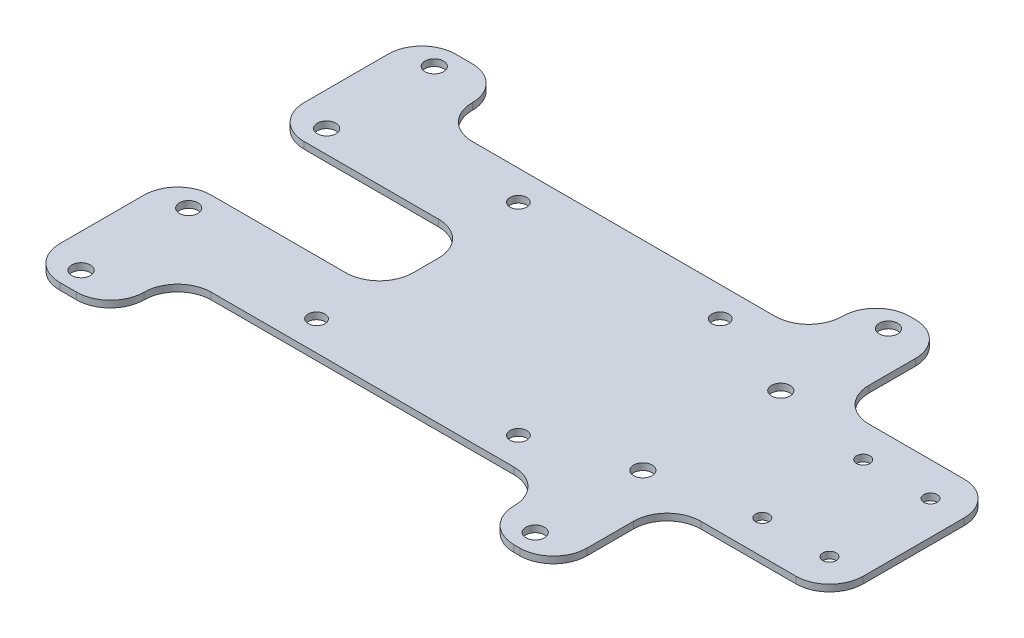
SolidWorks part; units mm, degrees
ref_plane "Front Plane" through (0, 0, 0) normal (0, 0, 1) x (1, 0, 0)
ref_plane "Top Plane" through (0, 0, 0) normal (0, 1, 0) x (1, 0, 0)
ref_plane "Right Plane" through (0, 0, 0) normal (1, 0, 0) x (0, 0, -1)
sketch "Sketch1" plane through (0, 0, 0) normal (0, 1, 0) x (1, 0, 0)
  line L2 (0, 0) -> (0, 140)
  line L12 (80, 0) -> (80, 140)
  line L14 (80, 0) -> (0, 0)
  line L15 (80, 140) -> (0, 140)
  point P0 (0, 0)
  dimension "D1" = 80
  dimension "D2" = 140
extrude "Boss-Extrude1" add sketch "Sketch1" along normal blind 2 contours L2 region at (40, 0, -70)
sketch "Sketch4" plane through (80, 0, 0) normal (1, 0, 0) x (0, 0, -1)
  line L1 (0, 0) -> (140, 0)
  line L2 (0, 0) -> (0, 2)
  line L3 (0, 2) -> (140, 2)
  line L4 (140, 0) -> (140, 2)
extrude "Boss-Extrude2" add sketch "Sketch4" along normal blind 35
sketch "Sketch5" plane through (115, 0, 0) normal (1, 0, 0) x (0, 0, -1)
  line L4 (0, 2) -> (0, 0)
  line L5 (0, 0) -> (140, 0)
  line L6 (140, 0) -> (140, 2)
  line L7 (140, 2) -> (0, 2)
  line L8 (0, 2) -> (0, 0)
  line L9 (0, 0) -> (140, 0)
  line L10 (140, 0) -> (140, 2)
  line L11 (140, 2) -> (0, 2)
  dimension "D1" = 0
extrude "Boss-Extrude3" add sketch "Sketch5" along normal blind 20
sketch "Sketch2" plane through (0, 0, 0) normal (0, -1, 0) x (1, 0, 0)
  line L0 (67.5, 0) -> (67.5, -140) construction
  line L1 (135, 0) -> (0, 0) construction
  line L2 (135, -140) -> (0, -140) construction
  line L4 (57.5, 0) -> (77.5, 0) construction
  line L5 (57.5, 0) -> (57.5, -140) construction
  line L6 (57.5, -140) -> (77.5, -140) construction
  line L7 (77.5, 0) -> (77.5, -140) construction
  line L8 (57.5, 0) -> (77.5, -140) construction
  line L9 (57.5, -140) -> (77.5, 0) construction
  line L10 (37.5, 0) -> (97.5, 0) construction
  line L11 (37.5, 0) -> (37.5, -140) construction
  line L12 (37.5, -140) -> (97.5, -140) construction
  line L13 (97.5, 0) -> (97.5, -140) construction
  line L14 (37.5, 0) -> (97.5, -140) construction
  line L15 (37.5, -140) -> (97.5, 0) construction
  circle A0 centre (97.5, -100) radius 2.5
  circle A1 centre (97.5, -40) radius 2.5
  circle A2 centre (37.5, -40) radius 2.5
  circle A3 centre (37.5, -100) radius 2.5
  point P6 (67.5, -70)
  point P11 (67.5, -70)
  dimension "D7" = 5
  dimension "D8" = 5
  dimension "D9" = 5
  dimension "D10" = 5
  dimension "D1" = 20
  dimension "D2" = 60
  dimension "D4" = 60
  dimension "D6" = 60
extrude "Cut-Extrude1" cut sketch "Sketch2" against normal blind 10
sketch "Sketch7" plane through (0, 0, 0) normal (-1, 0, 0) x (0, 0, 1)
  line L4 (-140, 0) -> (0, 0)
  line L5 (0, 0) -> (0, 2)
  line L6 (0, 2) -> (-140, 2)
  line L7 (-140, 2) -> (-140, 0)
  line L8 (-140, 0) -> (0, 0)
  line L9 (0, 0) -> (0, 2)
  line L10 (0, 2) -> (-140, 2)
  line L11 (-140, 2) -> (-140, 0)
  dimension "D1" = 0
extrude "Boss-Extrude5" add sketch "Sketch7" along normal blind 20
sketch "Sketch8" plane through (0, 0, 0) normal (0, -1, 0) x (1, 0, 0)
  line L0 (125, 0) -> (125, -140) construction
  line L1 (135, 0) -> (-20, 0) construction
  line L2 (135, -140) -> (-20, -140) construction
  line L3 (135, 0) -> (135, -140) construction
  line L4 (135, -140) -> (-20, -140) construction
  line L5 (57.5, -140) -> (57.5, 0) construction
  circle A0 centre (125, -17.5) radius 2.75
  circle A1 centre (125, -49.5) radius 2.75
  circle A2 centre (125, -90.5) radius 2.75
  circle A3 centre (125, -122.5) radius 2.75
  circle A8 centre (-10, -122.5) radius 2.75
  circle A9 centre (-10, -90.5) radius 2.75
  circle A10 centre (-10, -49.5) radius 2.75
  circle A11 centre (-10, -17.5) radius 2.75
  dimension "D6" = 5.5
  dimension "D7" = 5.5
  dimension "D8" = 5.5
  dimension "D9" = 5.5
  dimension "D1" = 10
  dimension "D2" = 41
  dimension "D3" = 32
  dimension "D4" = 17.5
  dimension "D5" = 32
extrude "Cut-Extrude2" cut sketch "Sketch8" against normal blind 10
sketch "Sketch9" plane through (135, 0, 0) normal (1, 0, 0) x (0, 0, -1)
  line L0 (140, 2) -> (0, 2) construction
  line L1 (45, 2) -> (95, 2)
  line L2 (45, 2) -> (45, 0)
  line L3 (45, 0) -> (95, 0)
  line L4 (95, 2) -> (95, 0)
  line L5 (0, 0) -> (140, 0) construction
  line L6 (0, 2) -> (0, 0) construction
  dimension "D1" = 50
  dimension "D2" = 45
extrude "Boss-Extrude6" add sketch "Sketch9" along normal blind 50
sketch "Sketch10" plane through (0, 0, 0) normal (0, -1, 0) x (1, 0, 0)
  line L0 (185, -45) -> (185, -95) construction
  line L1 (153, -55) -> (185, -55) construction
  line L3 (153, -85) -> (185, -85) construction
  line L4 (185, -55) -> (185, -85) construction
  circle A0 centre (175, -55) radius 2
  circle A1 centre (175, -85) radius 2
  circle A2 centre (155, -85) radius 2
  circle A3 centre (155, -55) radius 2
  dimension "D2" = 4
  dimension "D3" = 4
  dimension "D4" = 4
  dimension "D5" = 4
  dimension "D6" = 20
  dimension "D7" = 20
  dimension "D8" = 10
  dimension "D9" = 10
extrude "Cut-Extrude3" cut sketch "Sketch10" against normal blind 40
sketch "Sketch11" plane through (0, 0, 0) normal (0, -1, 0) x (1, 0, 0)
  line L0 (135, -11.2019) -> (22.2587, -11.2019)
  line L1 (135, 0) -> (135, -45) construction
  line L6 (-20, -140) -> (-20, 0) construction
  line L7 (-20, -11.2019) -> (-20, 0)
  line L8 (-20, 0) -> (135, 0)
  line L9 (135, 0) -> (135, -11.2019)
  line L10 (185, -70) -> (-20, -70) construction
  line L11 (185, -45) -> (185, -95) construction
  line L12 (135, -140) -> (135, -128.7981)
  line L13 (-20, -140) -> (135, -140)
  line L14 (-20, -128.7981) -> (-20, -140)
  line L19 (135, -128.7981) -> (22.2587, -128.7981)
  line L20 (22.2587, -11.2019) -> (-20, -11.2019)
  line L21 (22.2587, -128.7981) -> (-20, -128.7981)
extrude "Cut-Extrude4" cut sketch "Sketch11" against normal blind 40
chamfer "Chamfer1" distance 35 angle 55 2 edges at (135, 1, -95) (135, 1, -45) first distance on face at (135, 1, -111.8991) first distance on face at (135, 1, -28.1009)
sketch "Sketch12" plane through (0, 0, 0) normal (0, -1, 0) x (1, 0, 0)
  line L0 (-20, -128.7981) -> (-20, -11.2019) construction
  line L1 (-20, -56.2019) -> (40, -56.2019)
  line L2 (-20, -56.2019) -> (-20, -83.7981)
  line L3 (-20, -83.7981) -> (40, -83.7981)
  line L4 (40, -56.2019) -> (40, -83.7981)
  line L5 (136.7165, -128.7981) -> (-20, -128.7981) construction
  dimension "D1" = 45
  dimension "D2" = 45
  dimension "D3" = 60
extrude "Cut-Extrude5" cut sketch "Sketch12" against normal blind 10
sketch "Sketch13" plane through (0, 0, 0) normal (0, -1, 0) x (1, 0, 0)
  line L0 (184.9852, -45) -> (136.7165, -45)
  line L1 (136.7165, -45) -> (136.7165, -11.2019)
  line L2 (136.7165, -11.2019) -> (184.9852, -45)
  line L3 (184.9852, -95) -> (136.7165, -128.7981)
  line L4 (136.7165, -128.7981) -> (136.7165, -95)
  line L5 (136.7165, -95) -> (184.9852, -95)
extrude "Cut-Extrude6" cut sketch "Sketch13" against normal blind 10
sketch "Sketch14" plane through (0, 0, 0) normal (0, -1, 0) x (1, 0, 0)
  line L0 (-20, -11.2019) -> (136.7165, -11.2019) construction
  line L1 (5, -11.2019) -> (115, -11.2019)
  line L2 (5, -11.2019) -> (5, -31.2019)
  line L3 (5, -31.2019) -> (115, -31.2019)
  line L4 (115, -11.2019) -> (115, -31.2019)
  line L5 (136.7165, -128.7981) -> (-20, -128.7981) construction
  line L6 (115, -128.7981) -> (5, -128.7981)
  line L7 (115, -128.7981) -> (115, -108.7981)
  line L8 (115, -108.7981) -> (5, -108.7981)
  line L9 (5, -128.7981) -> (5, -108.7981)
  dimension "D1" = 20
  dimension "D2" = 20
  dimension "D3" = 5
  dimension "D4" = 0
  dimension "D5" = 110
  dimension "D6" = 110
extrude "Cut-Extrude7" cut sketch "Sketch14" against normal blind 10
fillet "Fillet1" radius 10 20 edges at (5, 1, -31.2019) (40, 1, -83.7981) (40, 1, -56.2019) (5, 1, -11.2019) (-20, 1, -11.2019) (-20, 1, -56.2019) (-20, 1, -83.7981) (-20, 1, -128.7981) (5, 1, -128.7981) (5, 1, -108.7981) (115, 1, -108.7981) (115, 1, -31.2019) (115, 1, -11.2019) (136.7165, 1, -11.2019) (136.7165, 1, -45) (185, 1, -45) (185, 1, -95) (115, 1, -128.7981) (136.7165, 1, -128.7981) (136.7165, 1, -95)
